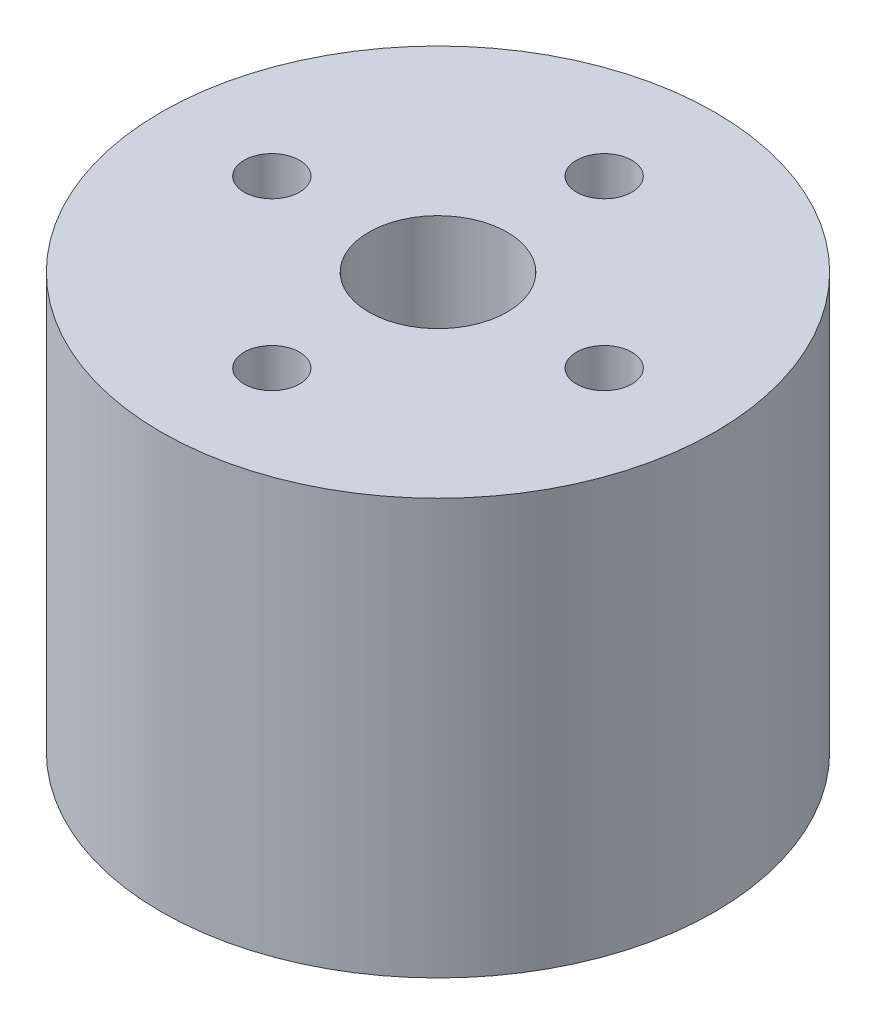
SolidWorks part; units mm, degrees
ref_plane "前视基准面" through (0, 0, 0) normal (0, 0, 1) x (1, 0, 0)
ref_plane "上视基准面" through (0, 0, 0) normal (0, 1, 0) x (1, 0, 0)
ref_plane "右视基准面" through (0, 0, 0) normal (1, 0, 0) x (0, 0, -1)
other "Configuration Table"
sketch "草图1" plane through (0, 0, 0) normal (0, 1, 0) x (1, 0, 0)
  circle A0 centre (0, 0) radius 10
  circle A1 centre (0, 0) radius 2.5
  dimension "D1" = 20
  dimension "D2" = 5
extrude "凸台-拉伸1" add sketch "草图1" along normal blind 15
sketch "草图2" plane through (0, 15, 0) normal (0, 1, 0) x (1, 0, 0)
  circle A0 centre (-6, 0) radius 1
  point P2 (0, 0)
  dimension "D1" = 2
  dimension "D2" = 6
extrude "切除-拉伸1" cut sketch "草图2" against normal blind 15
pattern_circular "阵列(圆周)1" count 4 over 360 about axis through (0, 15, 0) along (0, -1, 0) of "切除-拉伸1"
